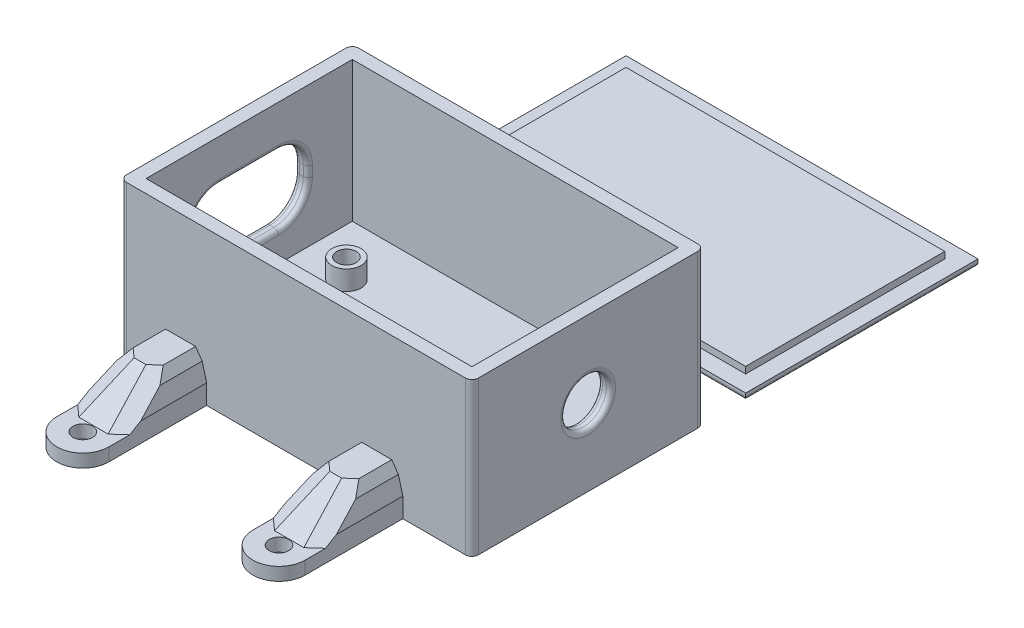
SolidWorks part; units mm, degrees
ref_plane "Alzado" through (0, 0, 0) normal (0, 0, 1) x (1, 0, 0)
ref_plane "Planta" through (0, 0, 0) normal (0, 1, 0) x (1, 0, 0)
ref_plane "Vista lateral" through (0, 0, 0) normal (1, 0, 0) x (0, 0, -1)
sketch "Croquis1" plane through (0, 0, 0) normal (0, 1, 0) x (1, 0, 0)
  line L1 (0, 0) -> (50, 0)
  line L2 (0, 0) -> (0, 31.65)
  line L3 (0, 31.65) -> (50, 31.65)
  line L4 (50, 0) -> (50, 31.65)
  circle A0 centre (7.3, 23.45) radius 1.5
  circle A1 centre (37.4, 8.05) radius 1.5
extrude "Saliente-Extruir1" add sketch "Croquis1" along normal blind 2
sketch "Croquis2" plane through (0, 0, 0) normal (0, -1, 0) x (1, 0, 0)
  line L1 (0, 0) -> (50, 0)
  line L2 (0, 0) -> (0, -31.65)
  line L3 (0, -31.65) -> (50, -31.65)
  line L4 (50, 0) -> (50, -31.65)
  line L13 (-2, 2) -> (52, 2)
  line L14 (-2, 2) -> (-2, -33.65)
  line L15 (-2, -33.65) -> (52, -33.65)
  line L16 (52, 2) -> (52, -33.65)
extrude "Saliente-Extruir2" add sketch "Croquis2" against normal blind 23.5
sketch "Croquis3" plane through (0, 2, 0) normal (0, 1, 0) x (1, 0, 0)
  circle A0 centre (7.3, 23.45) radius 2.25
  circle A1 centre (37.4, 8.05) radius 2.25
  circle A2 centre (7.3, 23.45) radius 1.5
  circle A3 centre (37.4, 8.05) radius 1.5
extrude "Saliente-Extruir3" add sketch "Croquis3" along normal blind 3
sketch "Croquis4" plane through (-2, 0, 0) normal (-1, 0, 0) x (0, 0, 1)
  line L0 (-33.65, 23.5) -> (-33.65, 0) construction
  line L1 (-20.325, 17.075) -> (-11.325, 17.075)
  line L2 (-24.825, 12.575) -> (-24.825, 11)
  line L3 (-20.325, 6.5) -> (-11.325, 6.5)
  line L4 (-6.825, 12.575) -> (-6.825, 11)
  line L5 (2, 0) -> (-33.65, 0) construction
  arc A0 (-24.825, 11) -> (-20.325, 6.5) centre (-20.325, 11) ccw
  arc A1 (-11.325, 6.5) -> (-6.825, 11) centre (-11.325, 11) ccw
  arc A2 (-11.325, 17.075) -> (-6.825, 12.575) centre (-11.325, 12.575) cw
  arc A3 (-20.325, 17.075) -> (-24.825, 12.575) centre (-20.325, 12.575) ccw
  dimension "D5" = 4.5
  dimension "D1" = 10.575
  dimension "D2" = 6.5
  dimension "D3" = 18
  dimension "D4" = 8.825
extrude "Cortar-Extruir1" cut sketch "Croquis4" against normal blind 3
sketch "Croquis5" plane through (52, 0, 0) normal (1, 0, 0) x (0, 0, -1)
  circle A0 centre (15.825, 11.75) radius 3.5
extrude "Cortar-Extruir2" cut sketch "Croquis5" against normal blind 3
fillet "Redondeo2" radius 0.7 16 edges at (0, 15.757, -8.143) (0, 11.7875, -6.825) (0, 7.818, -8.143) (0, 6.5, -15.825) (0, 7.818, -23.507) (0, 11.7875, -24.825) (0, 15.757, -23.507) (-2, 15.757, -8.143) (-2, 11.7875, -6.825) (-2, 7.818, -8.143) (-2, 6.5, -15.825) (-2, 7.818, -23.507) (-2, 11.7875, -24.825) (-2, 15.757, -23.507) (0, 17.075, -15.825) (-2, 17.075, -15.825)
sketch "Croquis6" plane through (0, 0, 0) normal (0, -1, 0) x (-1, 0, 0)
  line L1 (-52, -2) -> (2, -2) construction
  line L2 (-33.4, -2) -> (-33.4, -17)
  line L3 (-3.3, -2) -> (-3.3, -17)
  line L4 (-11.3, -2) -> (-11.3, -17)
  line L6 (-41.4, -2) -> (-41.4, -17)
  line L7 (-3.3, -2) -> (-11.3, -2)
  line L8 (-33.4, -2) -> (-41.4, -2)
  arc A1 (-11.3, -17) -> (-3.3, -17) centre (-7.3, -17) ccw
  arc A3 (-41.4, -17) -> (-33.4, -17) centre (-37.4, -17) ccw
  circle A4 centre (-7.3, -17) radius 1.5
  circle A5 centre (-37.4, -17) radius 1.5
  point P6 (-37.4, -2)
  point P7 (-7.3, -2)
extrude "Saliente-Extruir4" add sketch "Croquis6" against normal blind 2
sketch "Croquis7" plane through (0, 2, 0) normal (0, 1, 0) x (1, 0, 0)
  line L0 (33.4, -2) -> (41.4, -2) construction
  line L3 (41.4, -15.4348) -> (33.4, -15.4348)
  line L5 (33.4, -2) -> (33.4, -15.4348)
  line L6 (41.4, -2) -> (41.4, -15.4348)
  line L7 (33.4, -2) -> (41.4, -2)
  line L8 (3.3, -2) -> (11.3, -2) construction
  line L11 (3.3, -15.3601) -> (11.3, -15.3601)
  line L13 (11.3, -2) -> (11.3, -15.3601)
  line L14 (3.3, -2) -> (3.3, -15.3601)
  line L15 (11.3, -2) -> (3.3, -2)
  line L16 (11.3, -2) -> (11.3, -17) construction
  line L17 (41.4, -2) -> (41.4, -17) construction
  point P0 (37.4, -2)
  point P2 (7.3, -2)
  point P9 (11.3, -2)
  point P11 (3.3, -2)
  point P16 (11.3, -15.3601)
  point P21 (33.4, -2)
  point P23 (41.4, -2)
  point P26 (41.4, -15.4348)
extrude "Saliente-Extruir5" add sketch "Croquis7" along normal blind 5
chamfer "Chaflán1" distance 4 angle 15 4 edges at (41.4, 7, 8.7174) (33.4, 7, 8.7174) (3.3, 7, 8.68) (11.3, 7, 8.68) first distance on face at (41.4, 3, 11.4783) first distance on face at (33.4, 3, 11.4783) first distance on face at (3.3, 3, 11.4534) first distance on face at (11.3, 3, 11.4534)
chamfer "Chaflán2" distance 5 angle 55 2 edges at (7.3, 7, 15.3601) (37.4, 7, 15.4348) first distance on face at (7.3, 4, 15.3601) first distance on face at (37.4, 4, 15.4348)
chamfer "Chaflán3" distance 2 angle 25 4 edges at (40.8641, 5, 11.1503) (33.9359, 5, 11.1503) (10.7641, 5, 11.0756) (3.8359, 5, 11.0756) first distance on face at (37.4, 4, 12.5785) first distance on face at (7.3, 4, 12.5038)
fillet "Redondeo3" radius 0.7 2 edges at (50, 11.75, -19.325) (52, 11.75, -19.325)
sketch "Croquis10" plane through (0, 0, 0) normal (0, -1, 0) x (1, 0, 0)
  line L1 (-2, -40) -> (52, -40)
  line L2 (-2, -40) -> (-2, -75.65)
  line L3 (-2, -75.65) -> (52, -75.65)
  line L4 (52, -40) -> (52, -75.65)
extrude "Saliente-Extruir8" add sketch "Croquis10" against normal blind 1 separate body
sketch "Croquis11" plane through (0, 1, 0) normal (0, 1, 0) x (1, 0, 0)
  line L1 (0, 73.65) -> (50, 73.65)
  line L2 (0, 73.65) -> (0, 42)
  line L3 (0, 42) -> (50, 42)
  line L4 (50, 73.65) -> (50, 42)
  line L7 (0, 73.65) -> (0.5, 73.65)
  line L8 (0, 73.65) -> (0, 73.15)
  line L9 (0, 73.15) -> (0.5, 73.15)
  line L10 (0.5, 73.65) -> (0.5, 73.15)
  line L11 (50, 42) -> (49.5, 42)
  line L12 (50, 42) -> (50, 42.5)
  line L13 (50, 42.5) -> (49.5, 42.5)
  line L14 (49.5, 42) -> (49.5, 42.5)
  line L15 (49.5, 42.5) -> (0.5, 42.5)
  line L16 (49.5, 42.5) -> (49.5, 73.15)
  line L17 (49.5, 73.15) -> (0.5, 73.15)
  line L18 (0.5, 42.5) -> (0.5, 73.15)
extrude "Saliente-Extruir9" add sketch "Croquis11" along normal blind 1 contours L18 L15 L16 L17 region at (25, 1, -57.825)
fillet "Redondeo4" radius 1 4 edges at (-2, 11.75, -33.65) (-2, 11.75, 2) (52, 11.75, -33.65) (52, 11.75, 2)
chamfer "Chaflán4" distance 0.05 distance2 3 4 edges at (49.5, 2, -57.825) (25, 2, -73.15) (25, 2, -42.5) (0.5, 2, -57.825) first distance on face at (25, 2, -57.825)
fillet "Redondeo5" radius 0.5 4 edges at (25, 0, -40) (52, 0, -57.825) (25, 0, -75.65) (-2, 0, -57.825)
chamfer "Chaflán6" distance 1.5 angle 20 4 edges at (40.3282, 7, 4.2425) (34.4718, 7, 4.2425) (4.3718, 7, 4.2052) (10.2282, 7, 4.2052) first distance on face at (40.8641, 5, 5.6707) first distance on face at (33.9359, 5, 5.6707) first distance on face at (3.8359, 5, 5.6333) first distance on face at (10.7641, 5, 5.6333)
